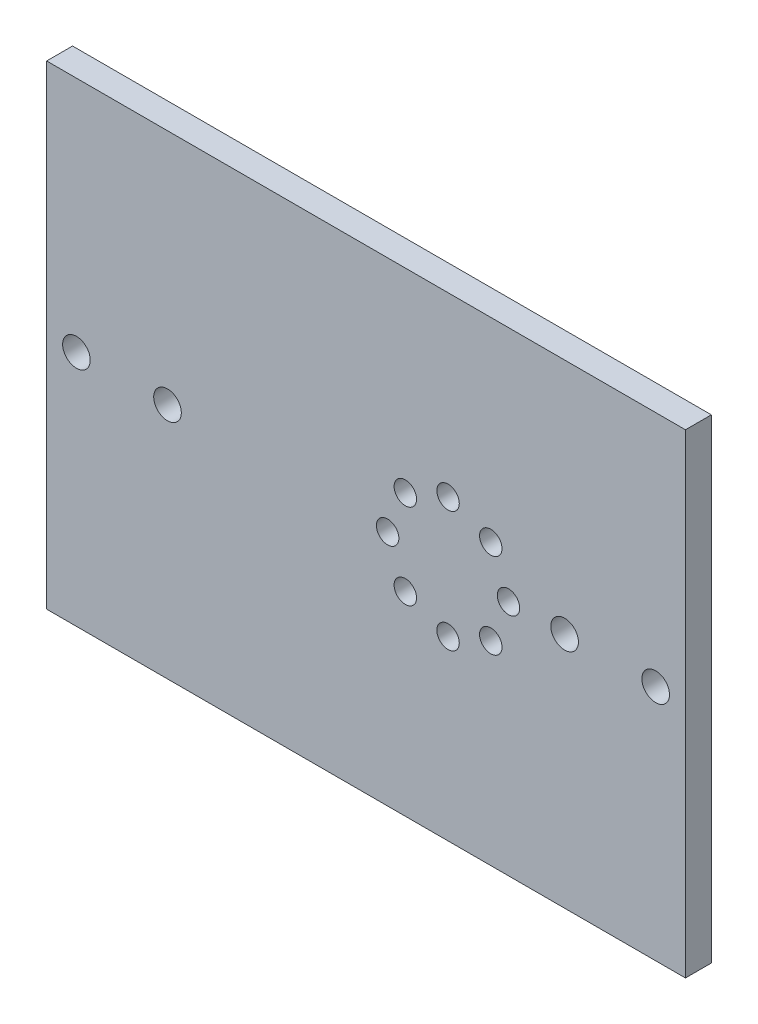
SolidWorks part; units mm, degrees
ref_plane "前基準面" through (0, 0, 0) normal (0, 0, 1) x (1, 0, 0)
ref_plane "上基準面" through (0, 0, 0) normal (0, 1, 0) x (1, 0, 0)
ref_plane "右基準面" through (0, 0, 0) normal (1, 0, 0) x (0, 0, -1)
sketch "草圖1" plane through (0, 0, 0) normal (0, 0, 1) x (1, 0, 0)
  line L1 (-37, 27.5) -> (37, 27.5)
  line L2 (-37, 27.5) -> (-37, -27.5)
  line L3 (-37, -27.5) -> (37, -27.5)
  line L4 (37, 27.5) -> (37, -27.5)
  line L5 (-37, 27.5) -> (37, -27.5) construction
  line L6 (-37, -27.5) -> (37, 27.5) construction
  point P0 (0, 0)
  dimension "D1" = 74
  dimension "D2" = 55
extrude "填料-伸長1" add sketch "草圖1" along normal blind 3
sketch "草圖2" plane through (0, 0, 3) normal (0, 0, 1) x (1, 0, 0)
  line L0 (-33.55, 0) -> (33.55, 0) construction
  line L3 (0, 27.5) -> (0, -27.5) construction
  line L4 (37, 27.5) -> (-37, 27.5) construction
  line L5 (-37, -27.5) -> (37, -27.5) construction
  circle A0 centre (-33.55, 0) radius 1.6
  circle A1 centre (33.55, 0) radius 1.6
  circle A2 centre (-23, 0) radius 1.6
  circle A3 centre (23, 0) radius 1.6
  circle A12 centre (16.5, 0) radius 1.3
  circle A13 centre (14.4497, -4.9497) radius 1.3
  circle A14 centre (9.5, -7) radius 1.3
  circle A15 centre (4.5503, -4.9497) radius 1.3
  circle A16 centre (2.5, 0) radius 1.3
  circle A17 centre (4.5503, 4.9497) radius 1.3
  circle A18 centre (9.5, 7) radius 1.3
  circle A19 centre (14.4497, 4.9497) radius 1.3
  point P8 (0, 0)
  point P10 (11.816, -8.6025)
  point P11 (0, 0)
  point P14 (0, 0)
  point P34 (9.5, 0)
  point P40 (9.5, 0)
  point P43 (9.5, 0)
  dimension "D3" = 3.2
  dimension "D7" = 7
  dimension "D6" = 2.6
  dimension "D1" = 67.1
  dimension "D2" = 46
  dimension "D4" = 23
  dimension "D5" = 9.5
  dimension "D8" = 8
extrude "除料-伸長1" cut sketch "草圖2" against normal through all contours A0 | A2 | A3 | A1
extrude "除料-伸長2" cut sketch "草圖2<3>" against normal through all contours A18 | A17 | A16 | A15 | A14 | A13 | A12 | A19 region at (16.5, 0, 3) region at (14.4497, -4.9497, 3) region at (9.5, -7, 3) region at (4.5503, -4.9497, 3) region at (2.5, 0, 3) region at (4.5503, 4.9497, 3) region at (9.5, 7, 3) region at (14.4497, 4.9497, 3)
sketch "草圖2<3>" plane through (0, 0, 3) normal (0, 0, 1) x (1, 0, 0) same geometry as "草圖2"
